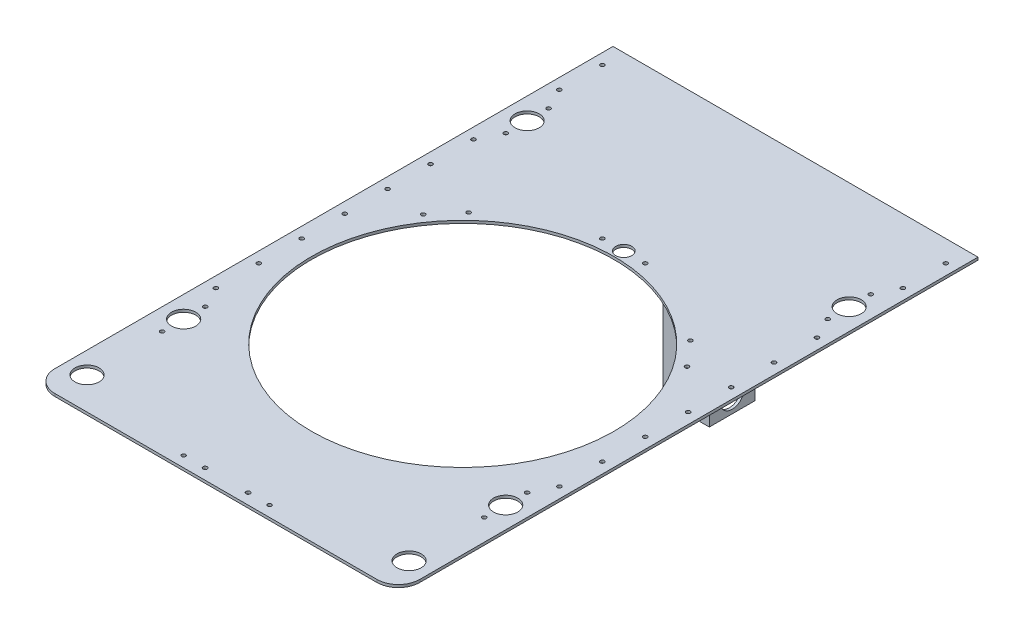
SolidWorks part; units mm, degrees
ref_plane "Front Plane" through (0, 0, 0) normal (0, 0, 1) x (1, 0, 0)
ref_plane "Top Plane" through (0, 0, 0) normal (0, 1, 0) x (1, 0, 0)
ref_plane "Right Plane" through (0, 0, 0) normal (1, 0, 0) x (0, 0, -1)
sketch "Sketch1" plane through (0, 0, 0) normal (0, 1, 0) x (1, 0, 0)
  line L1 (-215.9, 342.9) -> (215.9, 342.9)
  line L2 (-215.9, 342.9) -> (-215.9, -342.9)
  line L3 (-215.9, -342.9) -> (215.9, -342.9)
  line L4 (215.9, 342.9) -> (215.9, -342.9)
  line L5 (-215.9, 342.9) -> (215.9, -342.9) construction
  line L6 (-215.9, -342.9) -> (215.9, 342.9) construction
  point P0 (0, 0)
  dimension "D1" = 431.8
  dimension "D2" = 685.8
extrude "Boss-Extrude1" add sketch "Sketch1" along normal blind 3.175
sketch "Sketch2" plane through (0, 3.175, 0) normal (0, 1, 0) x (1, 0, 0)
  line L0 (0, -342.9) -> (0, 342.9) construction
  line L1 (-215.9, -342.9) -> (215.9, -342.9) construction
  line L2 (215.9, 342.9) -> (-215.9, 342.9) construction
  line L3 (-215.9, 342.9) -> (-215.9, -342.9) construction
  circle A0 centre (-190.5, -304.8) radius 14.3129
  circle A1 centre (-190.5, -190.5) radius 14.3129
  circle A2 centre (190.5, -304.8) radius 14.3129
  circle A3 centre (190.5, -190.5) radius 14.3129
  circle A4 centre (190.5, -190.5) radius 25.4 construction
  circle A5 centre (-190.5, -190.5) radius 25.4 construction
  circle A6 centre (190.5, -215.9) radius 2.3813
  circle A7 centre (190.5, -165.1) radius 2.3813
  circle A8 centre (-190.5, -215.9) radius 2.3813
  circle A9 centre (-190.5, -165.1) radius 2.3813
  dimension "D1" = 28.6258
  dimension "D2" = 28.6258
  dimension "D6" = 50.8
  dimension "D7" = 50.8
  dimension "D8" = 4.7625
  dimension "D9" = 4.7625
  dimension "D10" = 4.7625
  dimension "D11" = 4.7625
  dimension "D3" = 38.1
  dimension "D4" = 114.3
  dimension "D5" = 25.4
extrude "Cut-Extrude1" cut sketch "Sketch2" against normal through all
sketch "Sketch3" plane through (0, 0, 0) normal (0, -1, 0) x (-1, 0, 0)
  line L1 (29.8706, 270.2084) -> (-24.7394, 270.2084)
  line L2 (29.8706, 270.2084) -> (29.8706, 216.2334)
  line L3 (29.8706, 216.2334) -> (-24.7394, 216.2334)
  line L4 (-24.7394, 270.2084) -> (-24.7394, 216.2334)
  line L5 (29.8706, 270.2084) -> (-24.7394, 216.2334) construction
  line L6 (29.8706, 216.2334) -> (-24.7394, 270.2084) construction
  point P0 (2.5656, 243.2209)
  dimension "D1" = 53.975
  dimension "D2" = 54.61
extrude "Boss-Extrude2" add sketch "Sketch3" along normal blind 203.2
fillet "Fillet1" radius 20.32 4 edges at (24.7394, 0, -243.2209) (-2.5656, 0, -270.2084) (-2.5656, 0, -216.2334) (-29.8706, 0, -243.2209)
sketch "Sketch4" plane through (0, -203.2, 0) normal (0, -1, 0) x (-1, 0, 0)
  line L0 (-24.7394, 216.2334) -> (29.8706, 216.2334) construction
  line L1 (26.6956, 267.0334) -> (-21.5644, 267.0334)
  line L2 (26.6956, 267.0334) -> (26.6956, 219.4084)
  line L3 (26.6956, 219.4084) -> (-21.5644, 219.4084)
  line L4 (-21.5644, 267.0334) -> (-21.5644, 219.4084)
  line L5 (26.6956, 267.0334) -> (-21.5644, 219.4084) construction
  line L6 (26.6956, 219.4084) -> (-21.5644, 267.0334) construction
  line L7 (29.8706, 270.2084) -> (-24.7394, 270.2084) construction
  line L8 (29.8706, 216.2334) -> (29.8706, 270.2084) construction
  line L9 (-24.7394, 270.2084) -> (-24.7394, 216.2334) construction
  point P0 (2.5656, 243.2209)
  dimension "D1" = 3.175
  dimension "D2" = 3.175
  dimension "D3" = 3.175
  dimension "D4" = 3.175
extrude "Cut-Extrude2" cut sketch "Sketch4" against normal blind 203.2
sketch "Sketch5" plane through (-29.8706, 0, 0) normal (-1, 0, 0) x (0, 0, 1)
  line L0 (-216.2334, -203.2) -> (-216.2334, -20.32) construction
  line L1 (-216.2334, -203.2) -> (-270.2084, -203.2) construction
  circle A0 centre (-243.2209, -184.15) radius 14.2875
  dimension "D1" = 28.575
  dimension "D2" = 26.9875
  dimension "D3" = 19.05
extrude "Cut-Extrude3" cut sketch "Sketch5" against normal blind 203.2
sketch "Sketch6" plane through (0, 3.175, 0) normal (0, 1, 0) x (1, 0, 0)
  circle A0 centre (0, -50.8) radius 179.07
  dimension "D1" = 358.14
  dimension "D2" = 50.8
extrude "Cut-Extrude4" cut sketch "Sketch6" against normal through all
sketch "Sketch8" plane through (0, 3.175, 0) normal (0, 1, 0) x (1, 0, 0)
  circle A0 centre (0, 139.7) radius 9.525
  circle A2 centre (0, 139.7) radius 25.4 construction
  circle A3 centre (25.4, 139.7) radius 2.3813
  circle A4 centre (-25.4, 139.7) radius 2.3813
  dimension "D1" = 19.05
  dimension "D3" = 50.8
  dimension "D4" = 4.7625
  dimension "D5" = 4.7625
  dimension "D2" = 139.7
extrude "Cut-Extrude6" cut sketch "Sketch8" against normal through all
fillet "Fillet2" radius 25.4 2 edges at (215.9, 1.5875, 342.9) (-215.9, 1.5875, 342.9)
sketch "Sketch10" plane through (0, 3.175, 0) normal (0, 1, 0) x (1, 0, 0)
  line L0 (-215.9, 342.9) -> (-215.9, -317.5) construction
  line L1 (215.9, -317.5) -> (215.9, 342.9) construction
  circle A0 centre (-190.5, 215.9) radius 14.3129
  circle A1 centre (190.5, 215.9) radius 14.3129
  circle A2 centre (-190.5, 215.9) radius 25.4 construction
  circle A3 centre (190.5, 215.9) radius 25.4 construction
  circle A4 centre (190.5, 190.5) radius 2.3813
  circle A5 centre (190.5, 241.3) radius 2.3813
  circle A6 centre (-190.5, 190.5) radius 2.3813
  circle A7 centre (-190.5, 241.3) radius 2.3813
  circle A8 centre (190.5, -190.5) radius 14.3129 construction
  circle A9 centre (-190.5, -190.5) radius 14.3129 construction
  point P14 (0, 0)
  point P15 (-190.3345, 226.462)
  dimension "D1" = 28.6258
  dimension "D2" = 50.8
  dimension "D3" = 28.6258
  dimension "D4" = 50.8
  dimension "D5" = 4.7625
  dimension "D6" = 4.7625
  dimension "D7" = 4.7625
  dimension "D8" = 4.7625
  dimension "D9" = 25.4
  dimension "D10" = 25.4
  dimension "D11" = 406.4
  dimension "D12" = 406.4
extrude "Cut-Extrude8" cut sketch "Sketch10" against normal through all
sketch "Sketch11" plane through (0, 3.175, 0) normal (0, 1, 0) x (1, 0, 0)
  line L0 (0, -50.8) -> (156.0485, 58.4663) construction
  line L6 (0, 0) -> (0, 139.7) construction
  circle A0 centre (0, -50.8) radius 179.07
  circle A1 centre (0, -50.8) radius 179.07 construction
  circle A2 centre (0, -50.8) radius 184.15
  circle A3 centre (0, -50.8) radius 215.9
  circle A4 centre (156.0485, 58.4663) radius 2.3813
  circle A5 centre (131.1838, 87.3342) radius 2.3813
  circle A6 centre (0, -50.8) radius 190.5 construction
  circle A7 centre (-131.1838, 87.3342) radius 2.3813
  circle A8 centre (-156.0485, 58.4663) radius 2.3813
  dimension "D1" = 368.3
  dimension "D6" = 431.8
  dimension "D7" = 381
  dimension "D9" = 4.7625
  dimension "D10" = 4.7625
  dimension "D2" = 55
  dimension "D8" = 38.1
extrude "Cut-Extrude9" cut sketch "Sketch11" against normal through all contours A4 | A5 | A7 | A8 region at (156.0485, 3.175, -58.4663) region at (131.1838, 3.175, -87.3342) region at (-131.1838, 3.175, -87.3342) region at (-156.0485, 3.175, -58.4663)
sketch "Sketch13" plane through (0, 3.175, 0) normal (0, 1, 0) x (1, 0, 0)
  line L0 (-215.9, 342.9) -> (-215.9, -317.5) construction
  line L1 (215.9, 342.9) -> (-215.9, 342.9) construction
  line L2 (0, -342.9) -> (0, 342.9) construction
  line L3 (-190.5, -342.9) -> (190.5, -342.9) construction
  circle A0 centre (-203.2, 317.5) radius 2.3813
  circle A1 centre (-203.2, 266.7) radius 2.3813
  circle A2 centre (-203.2, 215.9) radius 2.3813 [skipped]
  circle A3 centre (-203.2, 165.1) radius 2.3813
  circle A4 centre (-203.2, 114.3) radius 2.3813
  circle A5 centre (-203.2, 63.5) radius 2.3813
  circle A6 centre (-203.2, 12.7) radius 2.3813
  circle A7 centre (-203.2, -38.1) radius 2.3813
  circle A8 centre (-203.2, -88.9) radius 2.3813
  circle A9 centre (-203.2, -139.7) radius 2.3813
  circle A10 centre (203.2, -139.7) radius 2.3813
  circle A11 centre (203.2, 12.7) radius 2.3813
  circle A12 centre (203.2, 63.5) radius 2.3813
  circle A13 centre (203.2, 114.3) radius 2.3813
  circle A14 centre (203.2, 165.1) radius 2.3813
  circle A15 centre (203.2, 266.7) radius 2.3813
  circle A16 centre (203.2, 317.5) radius 2.3813
  circle A17 centre (-25.4, -330.2) radius 2.4664
  circle A20 centre (-50.8, -330.2) radius 2.3078
  circle A21 centre (50.8, -330.2) radius 2.3078
  circle A22 centre (25.4, -330.2) radius 2.4664
  circle A23 centre (203.2, -88.9) radius 2.3813
  circle A24 centre (203.2, -38.1) radius 2.3813
  point P50 (0, 0)
  dimension "D1" = 4.7625
  dimension "D2" = 12.7
  dimension "D3" = 25.4
  dimension "D5" = 25.4
  dimension "D6" = 50.8
  dimension "D7" = 12.7
  dimension "D8" = 12.7
  dimension "D4" = 10
extrude "Cut-Extrude10" cut sketch "Sketch13" against normal through all
